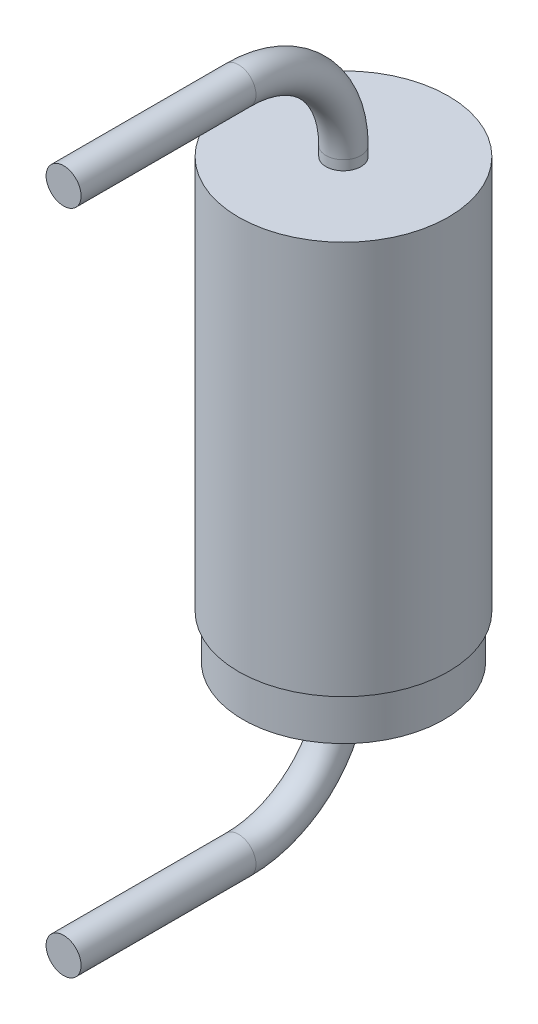
SolidWorks part; units mm, degrees
ref_plane "Front Plane" through (0, 0, 0) normal (0, 0, 1) x (1, 0, 0)
ref_plane "Top Plane" through (0, 0, 0) normal (0, 1, 0) x (1, 0, 0)
ref_plane "Right Plane" through (0, 0, 0) normal (1, 0, 0) x (0, 0, -1)
sketch "Sketch2" plane through (0, 0, 0) normal (0, 1, 0) x (1, 0, 0)
  circle A0 centre (0, 0) radius 1.2
  dimension "D1" = 2.4
extrude "Boss-Extrude1" add sketch "Sketch2" along normal blind 2.5 and the other way blind 2.5
sketch "Sketch3" plane through (0, 0, 0) normal (1, 0, 0) x (0, 0, -1)
  line L0 (0, 2.5) -> (0, 2.61)
  line L1 (1.2, 2.5) -> (-1.2, 2.5) construction
  line L2 (-1.2, 3.81) -> (-3.2, 3.81)
  arc A0 (0, 2.61) -> (-1.2, 3.81) centre (-1.2, 2.61) ccw
  dimension "D1" = 1.31
  dimension "D2" = 2
sweep "Sweep1" add path "Sketch3" circular profile diameter 0.4 parameters "D3"=0.4
mirror "Mirror1" about plane through (0, 0, 0) normal (0, 1, 0) of "Sweep1"
sketch "Sketch23" plane through (0, -2.5, 0) normal (0, -1, 0) x (1, 0, 0)
  circle A1 centre (0, 0) radius 1.2
  circle A2 centre (0, 0) radius 1.2 construction
  circle A4 centre (0, 0) radius 1.15
  dimension "D1" = 0.05
extrude "Cut-Extrude1" cut sketch "Sketch23" against normal blind 0.5
